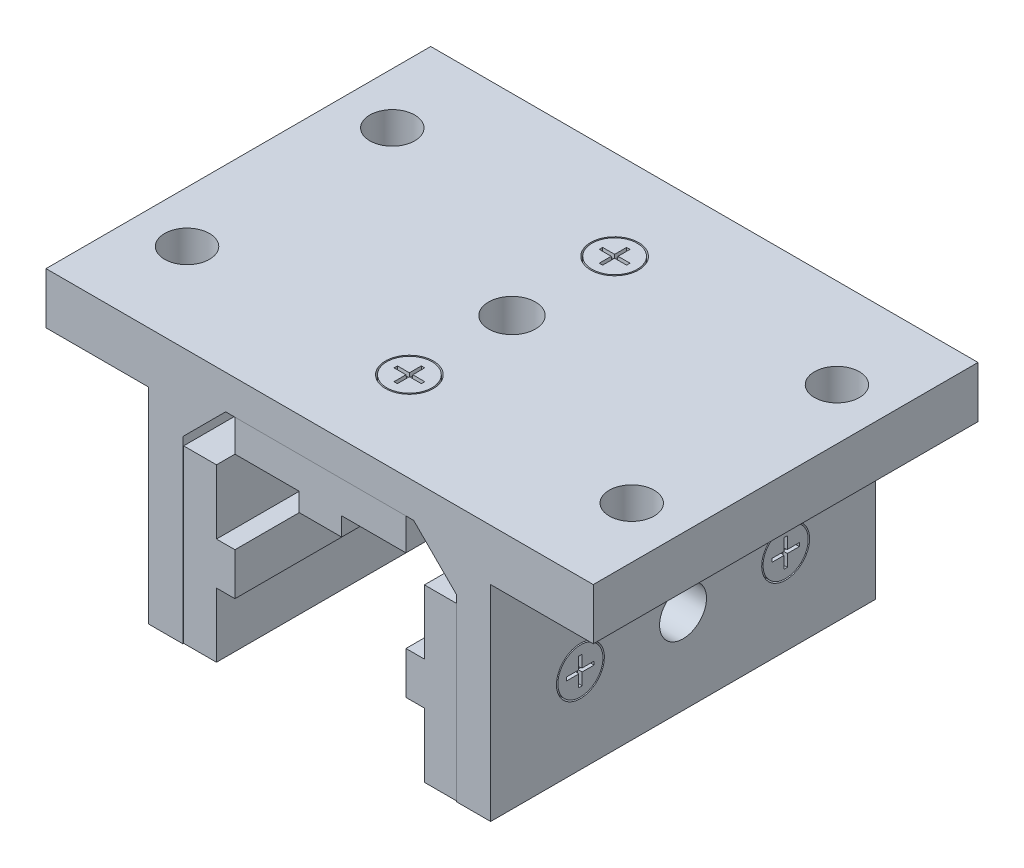
SolidWorks part; units mm, degrees
ref_plane "Front" through (0, 0, 0) normal (0, 0, 1) x (1, 0, 0)
ref_plane "Top" through (0, 0, 0) normal (0, 1, 0) x (1, 0, 0)
ref_plane "Right" through (0, 0, 0) normal (1, 0, 0) x (0, 0, -1)
sketch "Sketch1" plane through (0, 0, 0) normal (0, 0, 1) x (1, 0, 0)
  line L0 (-25.4, 0) -> (-25.4, 33.3248)
  line L1 (-31.75, 47.625) -> (31.75, 47.625)
  line L2 (-31.75, 47.625) -> (-31.75, 0)
  line L3 (-31.75, 0) -> (-25.4, 0)
  line L4 (31.75, 47.625) -> (31.75, 0)
  line L5 (-25.4, 33.3248) -> (-17.4498, 41.275)
  line L6 (-17.4498, 41.275) -> (17.4498, 41.275)
  line L7 (17.4498, 41.275) -> (25.4, 33.3248)
  line L8 (25.4, 33.3248) -> (25.4, 0)
  line L9 (25.4, 0) -> (31.75, 0)
  line L11 (-25.4, 0) -> (25.4, 0) construction
  dimension "D2" = 45
extrude "Boss-Extrude1" add sketch "Sketch1" along normal mid plane 71.4248
sketch "Sketch2" plane through (0, 0, 0) normal (0, 0, 1) x (1, 0, 0)
  line L0 (-19.304, 19.812) -> (-19.304, 31.75)
  line L1 (-25.4, 0) -> (-19.304, 0)
  line L2 (-25.4, 0) -> (-25.4, 31.75)
  line L3 (-25.4, 31.75) -> (-19.304, 31.75)
  line L4 (-19.304, 0) -> (-19.304, 11.938)
  line L5 (-19.304, 19.812) -> (-15.875, 19.812)
  line L7 (-19.304, 11.938) -> (-15.875, 11.938)
  line L8 (-15.875, 19.812) -> (-15.875, 11.938)
  line L12 (-17.4498, 41.275) -> (17.4498, 41.275) construction
  line L13 (-15.875, 41.275) -> (15.875, 41.275)
  line L14 (-15.875, 41.275) -> (-15.875, 35.179)
  line L15 (-15.875, 35.179) -> (-3.937, 35.179)
  line L16 (15.875, 41.275) -> (15.875, 35.179)
  line L17 (3.937, 35.179) -> (15.875, 35.179)
  line L19 (-3.937, 35.179) -> (-3.937, 31.75)
  line L20 (-3.937, 31.75) -> (3.937, 31.75)
  line L21 (3.937, 35.179) -> (3.937, 31.75)
  point P14 (-15.875, 15.875)
  point P28 (0, 41.275)
  dimension "Pad Wd" = 31.75
  dimension "Pad Thick 1" = 9.525
  dimension "Pad Thick 2" = 6.096
  dimension "Pad Nose" = 7.874
extrude "Boss-Extrude2" add sketch "Sketch2" along normal mid plane 71.12 separate body
sketch "Sketch11" plane through (-15.875, 0, 0) normal (1, 0, 0) x (0, 0, -1)
  line L0 (-35.56, 19.812) -> (35.56, 19.812) construction
  line L1 (-3.937, 19.812) -> (3.937, 19.812)
  line L2 (-3.937, 19.812) -> (-3.937, 11.938)
  line L3 (-3.937, 11.938) -> (3.937, 11.938)
  line L4 (3.937, 19.812) -> (3.937, 11.938)
  line L5 (-35.56, 11.938) -> (35.56, 11.938) construction
  point P8 (0, 19.812)
extrude "Cut-Extrude5" cut sketch "Sketch11" against normal through all
sketch "Sketch12" plane through (0, 31.75, 0) normal (0, -1, 0) x (1, 0, 0)
  line L0 (-3.937, 35.56) -> (-3.937, -35.56) construction
  line L1 (-3.937, 3.937) -> (3.937, 3.937)
  line L2 (-3.937, 3.937) -> (-3.937, -3.937)
  line L3 (-3.937, -3.937) -> (3.937, -3.937)
  line L4 (3.937, 3.937) -> (3.937, -3.937)
  line L5 (3.937, 35.56) -> (3.937, -35.56) construction
  point P8 (-3.937, 0)
extrude "Cut-Extrude6" cut sketch "Sketch12" against normal through all
mirror "Mirror1" about plane through (0, 0, 0) normal (1, 0, 0) of bodies 126 109
sketch "Sketch3" plane through (0, 47.625, 0) normal (0, 1, 0) x (1, 0, 0)
  line L0 (0, -19.05) -> (0, 19.05) construction
  circle A0 centre (0, -19.05) radius 4.445
  circle A1 centre (0, -19.05) radius 4.191
extrude "Cut-Extrude1" cut sketch "Sketch3" against normal blind 3.175
sketch "Sketch5" plane through (0, 47.625, 0) normal (0, 1, 0) x (1, 0, 0)
  line L0 (0.3175, -18.7325) -> (2.54, -18.7325)
  line L1 (-0.3175, -16.51) -> (0.3175, -16.51)
  line L2 (-0.3175, -16.51) -> (-0.3175, -18.7325)
  line L3 (-0.3175, -21.59) -> (0.3175, -21.59)
  line L4 (0.3175, -16.51) -> (0.3175, -18.7325)
  line L5 (-2.54, -18.7325) -> (-0.3175, -18.7325)
  line L6 (-2.54, -18.7325) -> (-2.54, -19.3675)
  line L7 (-2.54, -19.3675) -> (-0.3175, -19.3675)
  line L8 (2.54, -18.7325) -> (2.54, -19.3675)
  line L9 (-0.3175, -19.3675) -> (-0.3175, -21.59)
  line L10 (0.3175, -19.3675) -> (0.3175, -21.59)
  line L11 (0.3175, -19.3675) -> (2.54, -19.3675)
  line L12 (-0.3175, -18.7325) -> (0.3175, -19.3675) construction
  dimension "D1" = 0.635
  dimension "D2" = 5.08
extrude "Cut-Extrude2" cut sketch "Sketch5" against normal blind 0.762 draft 5
sketch "Sketch13" plane through (31.75, 0, 0) normal (1, 0, 0) x (0, 0, -1)
  circle A0 centre (-19.05, 15.875) radius 4.445
  dimension "D1" = 8.89
extrude "Cut-Extrude-Thin1" cut sketch "Sketch13" against normal blind 3.175 thin thin type one direction reverse wall 0.254
sketch "Sketch14" plane through (31.75, 0, 0) normal (1, 0, 0) x (0, 0, -1)
  line L0 (-19.3675, 15.5575) -> (-19.3675, 13.335)
  line L1 (-19.3675, 18.415) -> (-18.7325, 18.415)
  line L2 (-19.3675, 18.415) -> (-19.3675, 16.1925)
  line L3 (-19.3675, 13.335) -> (-18.7325, 13.335)
  line L4 (-18.7325, 18.415) -> (-18.7325, 16.1925)
  line L5 (-21.59, 16.1925) -> (-19.3675, 16.1925)
  line L6 (-21.59, 16.1925) -> (-21.59, 15.5575)
  line L7 (-21.59, 15.5575) -> (-19.3675, 15.5575)
  line L8 (-16.51, 16.1925) -> (-16.51, 15.5575)
  line L9 (-18.7325, 16.1925) -> (-16.51, 16.1925)
  line L10 (-18.7325, 15.5575) -> (-18.7325, 13.335)
  line L11 (-18.7325, 15.5575) -> (-16.51, 15.5575)
  line L12 (-19.3675, 16.1925) -> (-18.7325, 15.5575) construction
  dimension "D1" = 0.635
  dimension "D2" = 5.08
extrude "Cut-Extrude7" cut sketch "Sketch14" against normal blind 0.762 draft 5
mirror "Mirror4" about plane through (0, 0, 0) normal (1, 0, 0) of "Cut-Extrude7", "Cut-Extrude-Thin1"
mirror "Mirror3" about plane through (0, 0, 0) normal (0, 0, 1) of "Mirror4", "Cut-Extrude-Thin1", "Cut-Extrude7", "Cut-Extrude1", "Cut-Extrude2"
sketch "Sketch9" plane through (0, 47.625, 0) normal (0, 1, 0) x (1, 0, 0)
  circle A0 centre (0, 0) radius 4.3561
  dimension "Top Hole Dia" = 8.7122
extrude "Cut-Extrude4" cut sketch "Sketch9" against normal through all
sketch "Sketch15" plane through (0, 0, 0) normal (1, 0, 0) x (0, 0, -1)
  circle A0 centre (0, 15.875) radius 4.3561
  dimension "Side Wall Hole Dia" = 8.7122
extrude "Cut-Extrude8" cut sketch "Sketch15" against normal through all and the other way through all
sketch "Sketch16" plane through (0, 0, 0) normal (0, 0, 1) x (1, 0, 0)
  line L1 (-50.8, 47.625) -> (-28.575, 47.625)
  line L2 (-50.8, 47.625) -> (-50.8, 38.1)
  line L3 (-50.8, 38.1) -> (-28.575, 38.1)
  line L4 (-28.575, 47.625) -> (-28.575, 38.1)
  line L5 (31.75, 47.625) -> (-31.75, 47.625) construction
  line L6 (28.575, 47.625) -> (50.8, 47.625)
  line L7 (28.575, 47.625) -> (28.575, 38.1)
  line L8 (28.575, 38.1) -> (50.8, 38.1)
  line L9 (50.8, 47.625) -> (50.8, 38.1)
  line L10 (-31.75, 0) -> (-25.4, 0) construction
  line L11 (25.4, 0) -> (31.75, 0) construction
  point P4 (-28.575, 0)
  point P13 (28.575, 0)
  dimension "Oall Wd" = 101.6
  dimension "Top Flange Thickness" = 9.525
extrude "Top Flange" add sketch "Sketch16" along normal up to surface (35.7124 mm away) and the other way up to surface (35.7124 mm away) up to face at (0, 24.445, 35.7124) other way up to face at (0, 24.445, -35.7124)
sketch "Sketch17" plane through (0, 47.625, 0) normal (0, 1, 0) x (1, 0, 0)
  line L0 (-41.275, 19.05) -> (41.275, -19.05) construction
  line L1 (-41.275, 19.05) -> (41.275, 19.05) construction
  line L2 (-41.275, 19.05) -> (-41.275, -19.05) construction
  line L3 (-41.275, -19.05) -> (41.275, -19.05) construction
  line L4 (41.275, 19.05) -> (41.275, -19.05) construction
  line L5 (-28.575, 19.05) -> (-31.75, 19.05) construction
  circle A0 centre (41.275, 19.05) radius 4.1656
  circle A1 centre (41.275, -19.05) radius 4.1656
  circle A2 centre (-41.275, 19.05) radius 4.1656
  circle A3 centre (-41.275, -19.05) radius 4.1656
  dimension "Top Flange Hole Dia" = 8.3312
  dimension "Top Flange Hole Spacing" = 82.55
extrude "Top Flange Hole" cut sketch "Sketch17" against normal through all
ref_axis "Center Axis 1" through (-41.275, 38.1, 19.05) along (0, 1, 0)
ref_axis "Center Axis 2" through (41.275, 38.1, -19.05) along (0, 1, 0)
ref_axis "Center Axis 3" through (0, 41.275, 0) along (0, 1, 0)
equation "\"D1@Cut-Extrude1\" = \"Top Thick@Sketch1\" * .5"
equation "\"D1@Sketch13\" = \"Screw Head Dia@Sketch3\""
equation "\"D1@Cut-Extrude-Thin1\" = \"Leg Thick@Sketch1\" * .5"
equation "\"D5@Cut-Extrude-Thin1\" = \"D1@Sketch3\""
equation "\"D1@Cut-Extrude7\" = \"D1@Cut-Extrude2\""
equation "\"D1@Sketch14\" = \"D1@Sketch5\""
equation "\"D2@Sketch14\" = \"D2@Sketch5\""
equation "\"D3@Cut-Extrude7\" = \"D3@Cut-Extrude2\""
